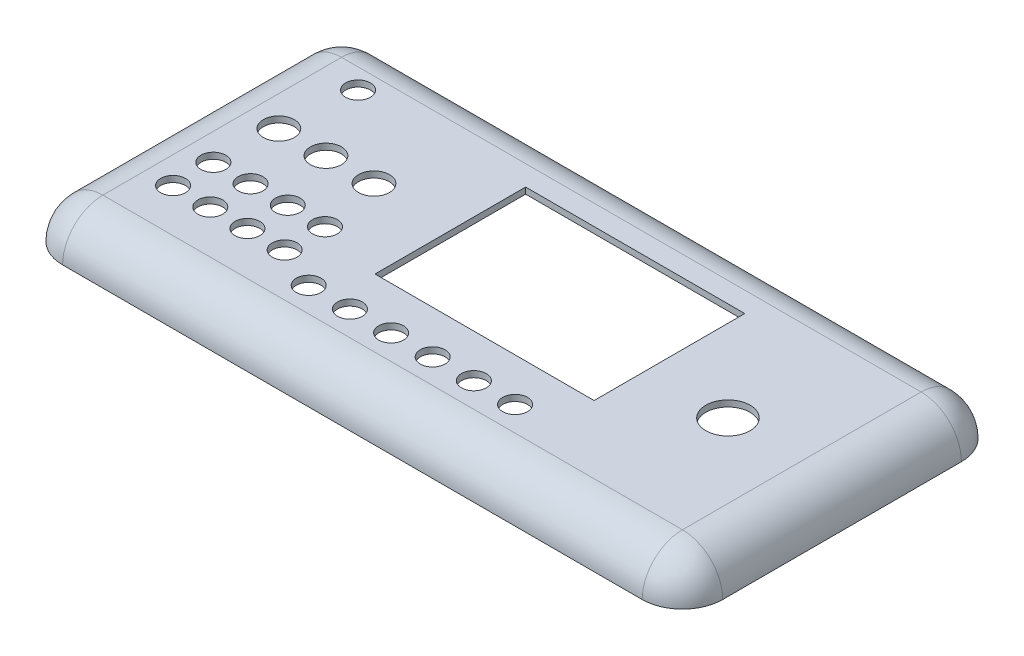
SolidWorks part; units mm, degrees
material "PET"
ref_plane "Спереди" through (0, 0, 0) normal (0, 0, 1) x (1, 0, 0)
ref_plane "Сверху" through (0, 0, 0) normal (0, 1, 0) x (1, 0, 0)
ref_plane "Справа" through (0, 0, 0) normal (1, 0, 0) x (0, 0, -1)
sketch "Эскиз1" plane through (0, 0, 0) normal (0, 1, 0) x (1, 0, 0)
  line L1 (-93.5, 38.5) -> (93.5, 38.5) construction
  line L2 (-93.5, 38.5) -> (-93.5, -38.5) construction
  line L3 (-93.5, -38.5) -> (93.5, -38.5) construction
  line L4 (93.5, 38.5) -> (93.5, -38.5) construction
  line L5 (-93.5, 38.5) -> (93.5, -38.5) construction
  line L6 (-93.5, -38.5) -> (93.5, 38.5) construction
  line L7 (-93.5, 49.5) -> (93.5, 49.5)
  line L8 (-104.5, 38.5) -> (-104.5, -38.5)
  line L9 (-93.5, -49.5) -> (93.5, -49.5)
  line L10 (104.5, 38.5) -> (104.5, -38.5)
  arc A0 (93.5, 49.5) -> (104.5, 38.5) centre (93.5, 38.5) cw
  arc A1 (104.5, -38.5) -> (93.5, -49.5) centre (93.5, -38.5) cw
  arc A2 (-93.5, -49.5) -> (-104.5, -38.5) centre (-93.5, -38.5) cw
  arc A3 (-93.5, 49.5) -> (-104.5, 38.5) centre (-93.5, 38.5) ccw
  point P0 (0, 0)
  dimension "D4" = 11
  dimension "D1" = 77
  dimension "D2" = 187
  dimension "D3" = 11
extrude "Бобышка-Вытянуть1" add sketch "Эскиз1" along normal blind 11
fillet "Скругление1" radius 11 8 edges at (104.5, 11, 0) (101.2782, 11, 46.2782) (0, 11, 49.5) (-101.2782, 11, 46.2782) (-104.5, 11, 0) (-101.2782, 11, -46.2782) (0, 11, -49.5) (101.2782, 11, -46.2782)
shell "Оболочка1" thickness 2 removed face at (0, 0, 0) outward yes
sketch "Эскиз2" plane through (0, 13, 0) normal (0, 1, 0) x (1, 0, 0)
  line L0 (-27.56, 31.96) -> (43.14, 31.96) construction
  line L1 (-27.56, -16.64) -> (43.14, -16.64)
  line L2 (-27.56, -16.64) -> (-27.56, 31.96)
  line L3 (-27.56, 31.96) -> (43.14, 31.96)
  line L4 (43.14, -16.64) -> (43.14, 31.96)
  line L5 (43.14, -16.64) -> (-27.56, -16.64) construction
  line L6 (-27.56, -16.64) -> (-27.56, 31.96) construction
  line L7 (43.14, 31.96) -> (43.14, -16.64) construction
extrude "Вырез-Вытянуть1" cut sketch "Эскиз2" against normal through all
sketch "Эскиз3" plane through (0, 13, 0) normal (0, 1, 0) x (1, 0, 0)
  circle A0 centre (-83.7184, 8.4914) radius 5
  circle A1 centre (-68.5184, 8.4914) radius 5
  circle A2 centre (-53, 8.46) radius 5
  arc A3 (-81.4969, 10.5075) -> (-83.0832, 5.5594) centre (-83.7184, 8.4914) ccw construction
  arc A4 (-66.2969, 10.5075) -> (-67.8832, 5.5594) centre (-68.5184, 8.4914) ccw construction
  arc A5 (-55.7359, 9.6908) -> (-50.5661, 10.214) centre (-53, 8.46) ccw construction
  circle A6 centre (-81.6886, 32.0227) radius 4
  circle A7 centre (-84.8496, -11.5003) radius 4
  circle A8 centre (-72.8496, -11.5003) radius 4
  circle A9 centre (-60.8496, -11.5003) radius 4
  circle A10 centre (-48.8496, -11.5003) radius 4
  circle A11 centre (-84.8504, -24.4997) radius 4
  circle A12 centre (-72.8504, -24.4997) radius 4
  circle A13 centre (-60.8504, -24.4997) radius 4
  circle A14 centre (-48.8504, -24.4997) radius 4
  circle A15 centre (-35.0996, -30.5003) radius 4
  circle A16 centre (-21.7996, -30.5003) radius 4
  circle A17 centre (-8.4996, -30.5003) radius 4
  circle A18 centre (4.9004, -30.5003) radius 4
  circle A19 centre (18.2004, -30.5003) radius 4
  circle A20 centre (31.5004, -30.5003) radius 4
  circle A21 centre (69.6, 0.0797) radius 7.14
  circle A22 centre (-60.8496, -11.5003) radius 1.7145 construction
  circle A23 centre (-48.8496, -11.5003) radius 1.7145 construction
  circle A24 centre (-84.8504, -24.4997) radius 1.7145 construction
  circle A25 centre (-72.8504, -24.4997) radius 1.7145 construction
  circle A26 centre (-60.8504, -24.4997) radius 1.7145 construction
  circle A27 centre (-48.8504, -24.4997) radius 1.7145 construction
  circle A30 centre (-35.0996, -30.5003) radius 1.7145 construction
  circle A31 centre (-21.7996, -30.5003) radius 1.7145 construction
  circle A32 centre (-8.4996, -30.5003) radius 1.7145 construction
  circle A33 centre (4.9004, -30.5003) radius 1.7145 construction
  circle A34 centre (18.2004, -30.5003) radius 1.7145 construction
  circle A35 centre (31.5004, -30.5003) radius 1.7145 construction
  circle A36 centre (69.6, 0.0797) radius 3 construction
  circle A38 centre (69.6, 0.0797) radius 7.14 construction
  dimension "D1" = 10
  dimension "D2" = 8
extrude "Вырез-Вытянуть2" cut sketch "Эскиз3" against normal through all
